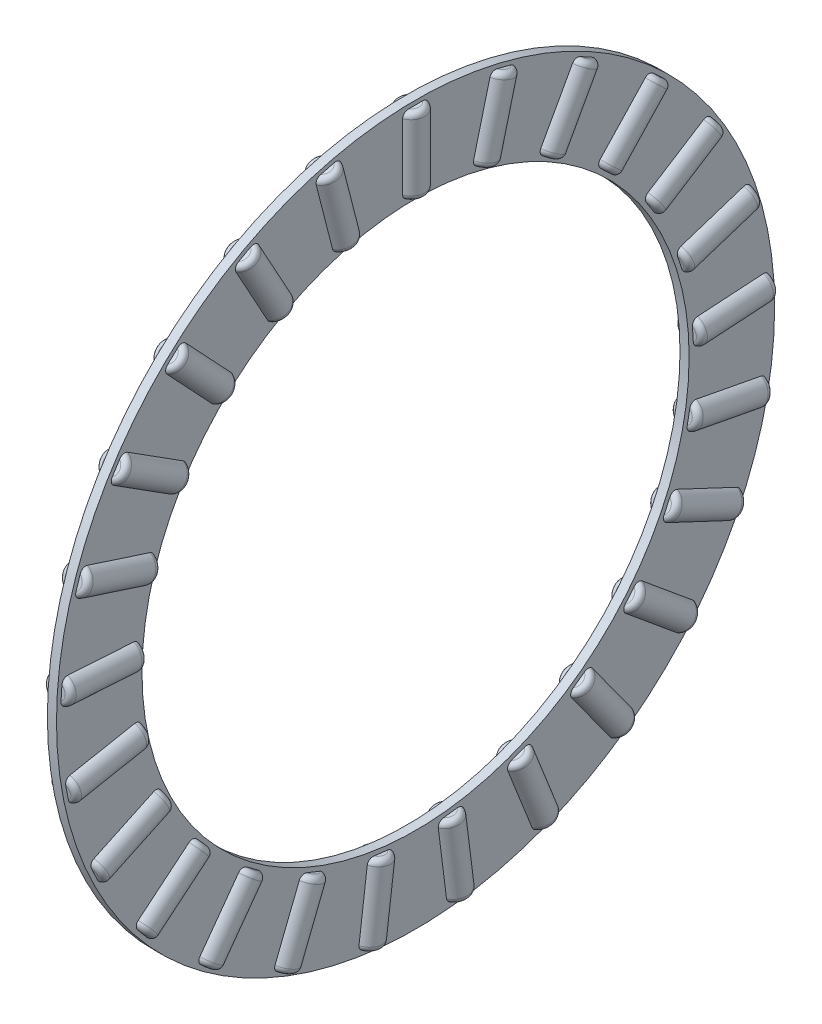
SolidWorks part; units mm, degrees
ref_plane "Plane1" through (0, 0, 0) normal (0, 0, 1) x (1, 0, 0)
ref_plane "Plane2" through (0, 0, 0) normal (0, 1, 0) x (1, 0, 0)
ref_plane "Plane3" through (0, 0, 0) normal (1, 0, 0) x (0, 0, -1)
sketch "Clipboard" plane through (0, 0, 0) normal (0, 0, 1) x (1, 0, 0)
  line L0 (-10, 0) -> (10, 0) construction
  line L1 (0, 0) -> (20.2657, -9.45)
  line L2 (0, 0) -> (41.9167, 19.5461)
  line L3 (0, 0) -> (20.2657, -9.45)
  line L4 (0, 0) -> (-22.3471, -0.7804)
  dimension "BallCLRad" = 46.25
sketch "CagSpiSke" plane through (0, 0, 0) normal (0, 0, 1) x (1, 0, 0)
  line L5 (-34.925, 0) -> (34.925, 0) construction
  line L6 (-0.6667, 52.5) -> (0.6667, 52.5)
  line L7 (-0.6667, 52.5) -> (-0.6667, 40)
  line L8 (-0.6667, 40) -> (0.6667, 40)
  line L9 (0.6667, 52.5) -> (0.6667, 40)
  dimension "ID" = 80
  dimension "OD" = 105
revolve "CageSpine" add sketch "CagSpiSke" angle 360 about L5 reverse direction yes
ref_axis "Axis1" through (-50, 0, 0) along (1, 0, 0)
sketch "RolDetSke" plane through (0, 0, 0) normal (0, 0, 1) x (1, 0, 0)
  line L0 (0, 33.02) -> (0, 55.88) construction
  line L3 (0, 51.875) -> (1.2, 51.875)
  line L4 (0, 51.875) -> (0, 40.625)
  line L5 (0, 40.625) -> (1.2, 40.625)
  line L6 (2, 51.075) -> (2, 41.425)
  arc A0 (2, 41.425) -> (1.2, 40.625) centre (1.2, 41.425) cw
  arc A1 (1.2, 51.875) -> (2, 51.075) centre (1.2, 51.075) cw
  dimension "offset" = 40.625
  dimension "Roller_diameter" = 4
  dimension "Cyl_Len" = 11.25
revolve "RollerDetailed" add sketch "RolDetSke" angle 360 about L0 reverse direction yes
pattern_circular "RollersDetailed" count 25 every 14.4 about axis through (-50, 0, 0) along (1, 0, 0) of "RollerDetailed"
sketch "RolSimSke" plane through (0, 0, 0) normal (0, 0, 1) x (1, 0, 0)
  line L1 (-17.78, 0) -> (12.7, 0) construction
  line L3 (-1.2, 51.875) -> (1.2, 51.875)
  line L4 (-2, 51.075) -> (-2, 41.425)
  line L5 (-1.2, 40.625) -> (1.2, 40.625)
  line L6 (2, 51.075) -> (2, 41.425)
  arc A0 (-2, 41.425) -> (-1.2, 40.625) centre (-1.2, 41.425) ccw
  arc A1 (-1.2, 51.875) -> (-2, 51.075) centre (-1.2, 51.075) ccw
  arc A2 (2, 51.075) -> (1.2, 51.875) centre (1.2, 51.075) ccw
  arc A3 (1.2, 40.625) -> (2, 41.425) centre (1.2, 41.425) ccw
  dimension "Halfdia" = 2
  dimension "offset" = 40.625
  dimension "Roller_diameter" = 4
  dimension "Cyl_Len" = 11.25
revolve "RollersSimplified" [suppressed] add sketch "RolSimSke" angle 360 about L1
equation "\"BallCLRad@Clipboard\" =  ( \"OD@CagSpiSke\" + \"ID@CagSpiSke\" )  / 4"
equation "\"offset@RolSimSke\" = \"BallCLRad@Clipboard\" - \"Cyl_Len@RolSimSke\" / 2"
equation "\"offset@RolDetSke\" = \"BallCLRad@Clipboard\" - \"Cyl_Len@RolDetSke\" / 2"
equation "\"Thickness@CagSpiSke\" =  \"Roller_diameter@RolDetSke\"  / 3"
equation "\"HalfThick@CagSpiSke\" = \"Thickness@CagSpiSke\" / 2"
equation "\"radius@RolDetSke\" =  ( \"Roller_diameter@RolDetSke\" - \"Thickness@CagSpiSke\" )  * 0.6 / 2"
equation "\"Roller_diameter@RolSimSke\" = \"Roller_diameter@RolDetSke\""
equation "\"Cyl_Len@RolSimSke\" = \"Cyl_Len@RolDetSke\""
equation "\"Rol_rad@RolSimSke\" = \"radius@RolDetSke\""
equation "\"Halfdia@RolSimSke\" = \"Roller_diameter@RolSimSke\" / 2"
equation "\"Max_count@Clipboard\" = int( 3.14159265 / atn(( \"Roller_diameter@RolDetSke\" / 2) / sqr( \"offset@RolDetSke\"  *  \"offset@RolDetSke\" - ( \"Roller_diameter@RolDetSke\" / 2) *  ( \"Roller_diameter@RolDetSke\" / 2))))"
equation "\"Max_count@Clipboard\" = ((sgn( \"Max_count@Clipboard\" - \"Count@Clipboard\" )-1)*( \"Max_count@Clipboard\" - \"Count@Clipboard\" ))/-2+ \"Count@Clipboard\""
equation "\"Count@RollersDetailed\" = int( \"Show_count@Clipboard\" ) "
equation "\"Count@RollersDetailed\" = ((sgn( \"Count@RollersDetailed\" - \"Max_count@Clipboard\" )-1)*( \"Count@RollersDetailed\" - \"Max_count@Clipboard\" ))/-2+ \"Max_count@Clipboard\""
equation "\"Count@RollersDetailed\" = ((sgn( \"Count@RollersDetailed\" - \"Min_count@Clipboard\" )+1)*( \"Count@RollersDetailed\" - \"Min_count@Clipboard\"))/2 +\"Min_count@Clipboard\""
equation "\"Angle@RollersDetailed\" = 360.0 / \"Max_count@Clipboard\""
